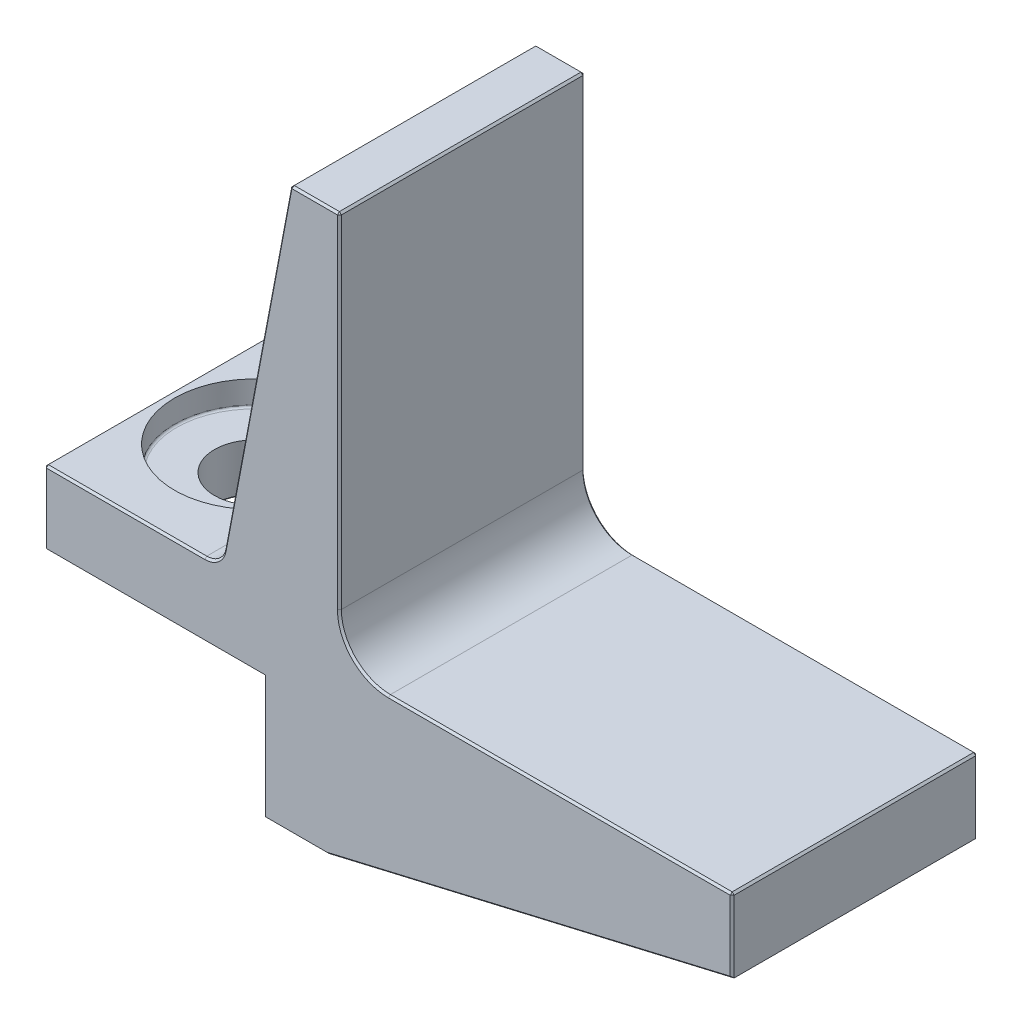
SolidWorks part; units mm, degrees
material "7075-T6 (SN)"
ref_plane "Front Plane" through (0, 0, 0) normal (0, 0, 1) x (1, 0, 0)
ref_plane "Top Plane" through (0, 0, 0) normal (0, 1, 0) x (1, 0, 0)
ref_plane "Right Plane" through (0, 0, 0) normal (1, 0, 0) x (0, 0, -1)
sketch "Sketch1" plane through (0, 0, 0) normal (0, 0, 1) x (1, 0, 0)
  line L0 (0, 0) -> (50.8, 0)
  line L1 (50.8, 0) -> (50.8, -9.525)
  line L2 (-9.8398, -5.8961) -> (-38.1608, -5.8961)
  line L3 (-38.1608, -5.8961) -> (-38.1608, 3.6289)
  line L4 (-38.1608, 3.6289) -> (-15.3008, 3.6289)
  line L5 (-15.3008, 3.6289) -> (-6.35, 50.8)
  line L6 (-6.35, 50.8) -> (0, 50.8)
  line L7 (0, 50.8) -> (0, 0)
  line L8 (-9.8398, -5.8961) -> (-9.8398, -21.7711)
  line L9 (-9.8398, -21.7711) -> (-1.5848, -21.7711)
  line L10 (-1.5848, -21.7711) -> (50.8, -9.525)
  dimension "D1" = 50.8
  dimension "D2" = 50.8
  dimension "D3" = 9.525
  dimension "D4" = 38.1608
  dimension "D5" = 6.35
  dimension "D6" = 22.86
  dimension "D7" = 28.321
  dimension "D8" = 9.525
  dimension "D9" = 15.875
  dimension "D10" = 8.255
  dimension "D11" = 3.6289
extrude "Boss-Extrude1" add sketch "Sketch1" along normal blind 31.75
hole_wizard "CBORE for 3/8 Binding Head Machine Screw1" positions "Sketch6" profile "Sketch3" counterbore size "3/8" standard "ANSI Inch" end condition through all
sketch "Sketch6" plane through (0, 3.6289, 0) normal (0, 1, 0) x (1, 0, 0)
  line L1 (-38.1608, -31.75) -> (-38.1608, 0) construction
  point P0 (-26.8578, -15.875)
  point P8 (-38.1608, -15.875)
  dimension "D1" = 11.303
sketch "Sketch3" plane through (-26.8578, 3.6289, 15.875) normal (1, 0, 0) x (0, 0, 1)
  line L0 (0, 0) -> (0, 25.4)
  line L1 (0, 25.4) -> (5.1689, 25.4)
  line L3 (5.1689, 25.4) -> (5.1689, 3.175)
  line L4 (10.3378, 3.175) -> (5.1689, 3.175)
  line L5 (10.3378, 3.175) -> (10.3378, 0)
  line L7 (10.3378, 0) -> (0, 0)
  line L11 (0, 0) -> (0, 107.95) construction
  dimension "Thru Hole Dia." = 10.3378
  dimension "Thru Hole Depth" = 25.4
  dimension "C'Bore Depth" = 3.175
fillet "Fillet1" radius 2.54 1 edges at (-15.3008, 3.6289, 15.875)
fillet "Fillet2" radius 6.35 1 edges at (0, 0, 15.875)
chamfer "Chamfer1" distance 0.254 angle 45 31 edges at (-6.35, 50.8, 15.875) (-3.175, 50.8, 0) (-10.6293, 28.2477, 0) (-15.7842, 4.2126, 0) (-27.7825, 3.6289, 0) (-38.1608, -1.1336, 0) (-24.0003, -5.8961, 0) (50.8, -4.7625, 0) (28.575, 0, 0) (1.8599, 1.8599, 0) (0, 28.575, 0) (50.8, -4.7625, 31.75) (-24.0003, -5.8961, 31.75) (-38.1608, -5.8961, 15.875) (-38.1608, -1.1336, 31.75) (-38.1608, 3.6289, 15.875) (-27.7825, 3.6289, 31.75) (-15.7842, 4.2126, 31.75) (-10.6293, 28.2477, 31.75) (-3.175, 50.8, 31.75) (0, 50.8, 15.875) (0, 28.575, 31.75) (1.8599, 1.8599, 31.75) (28.575, 0, 31.75) (50.8, 0, 15.875) (-9.8398, -13.8336, 0) (-5.7123, -21.7711, 0) (24.6076, -15.6481, 0) (24.6076, -15.6481, 31.75) (-5.7123, -21.7711, 31.75) (-9.8398, -13.8336, 31.75) first distance on face at (-3.175, 50.8, 15.875) first distance on face at (-12.0593, 20.712, 15.5785) first distance on face at (-15.9703, 4.4374, 5.8459) first distance on face at (-27.6216, 3.6289, 15.875) first distance on face at (-38.1608, -1.1336, 15.875) first distance on face at (-32.0267, -5.8961, 15.875) first distance on face at (50.8, -4.7625, 15.875) first distance on face at (-2.2494, 4.1753, 0) first distance on face at (2.5174, 2.5174, 15.875) first distance on face at (0, 28.575, 15.875) first distance on face at (-15.9703, 4.4374, 25.9041) first distance on face at (-2.2494, 4.1753, 31.75) first distance on face at (-9.8398, -13.8336, 15.875) first distance on face at (-5.7123, -21.7711, 15.875) first distance on face at (24.6076, -15.6481, 15.875)
fillet "Fillet3" radius 0.254 1 edges at (-26.8578, 0.4539, 26.2128)
chamfer "Chamfer2" distance 0.254 angle 45 1 edges at (-32.0267, -5.8961, 15.875)
